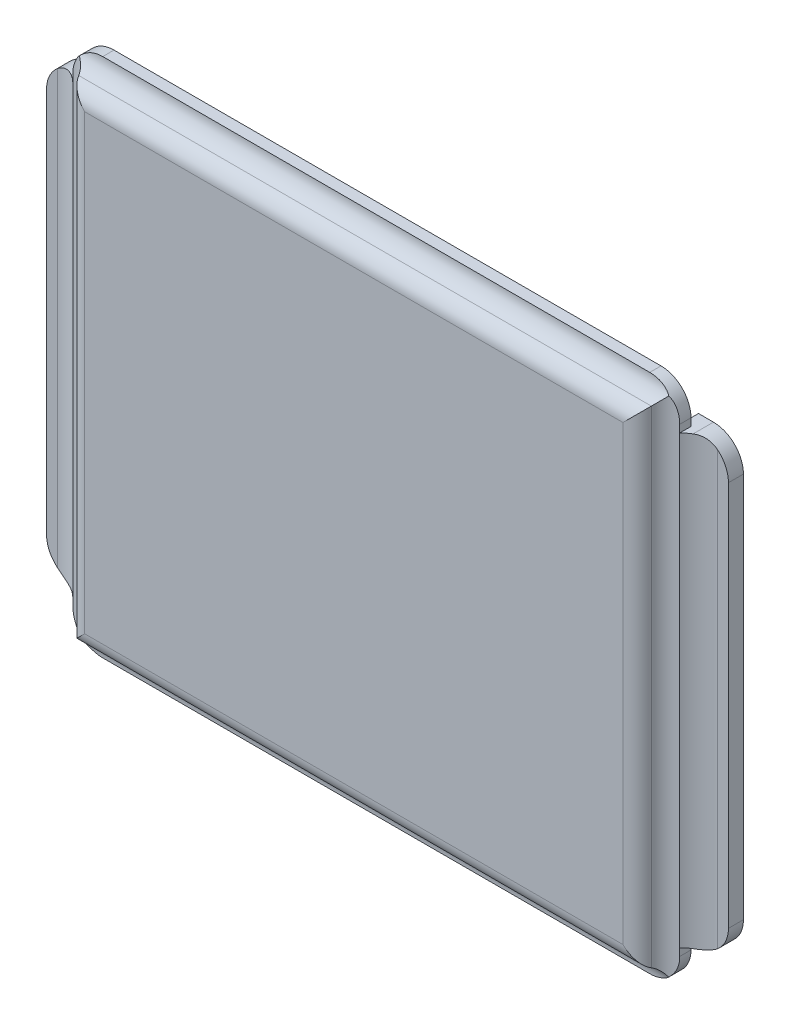
SolidWorks part; units mm, degrees
ref_plane "Front Plane" through (0, 0, 0) normal (0, 0, 1) x (1, 0, 0)
ref_plane "Top Plane" through (0, 0, 0) normal (0, 1, 0) x (1, 0, 0)
ref_plane "Right Plane" through (0, 0, 0) normal (1, 0, 0) x (0, 0, -1)
sketch "Sketch1" plane through (0, 0, 0) normal (0, 0, 1) x (1, 0, 0)
  line L0 (0, 5.95) -> (9.1, 5.95) construction
  line L1 (0, 0) -> (0.6, 0)
  line L2 (0, 0) -> (0, 5.95)
  line L3 (0, 5.95) -> (0.6, 5.95)
  line L4 (0.6, 0) -> (0.6, 5.95)
  line L6 (9.1, 5.95) -> (8.5, 5.95)
  line L7 (9.1, 5.95) -> (9.1, 0)
  line L8 (9.1, 0) -> (8.5, 0)
  line L9 (8.5, 5.95) -> (8.5, 0)
extrude "Boss-Extrude1" add sketch "Sketch1" along normal blind 0.2
sketch "Sketch2" plane through (0, 0, 0.2) normal (0, 0, 1) x (1, 0, 0)
  line L0 (8.6, 6.45) -> (8.6, -0.5)
  line L1 (0.5, -0.5) -> (1.2, -0.5)
  line L2 (0.5, -0.5) -> (0.5, 6.45)
  line L3 (0.5, 6.45) -> (1.2, 6.45)
  line L4 (1.2, 6.45) -> (7.9, 6.45)
  line L5 (7.9, -0.5) -> (1.2, -0.5)
  line L6 (8.6, -0.5) -> (7.9, -0.5)
  line L8 (8.6, 6.45) -> (7.9, 6.45)
extrude "Boss-Extrude2" add sketch "Sketch2" along normal blind 0.15
fillet "Fillet1" radius 0.5 1 edges at (0.5, 2.975, 0.2)
fillet "Fillet2" radius 0.5 1 edges at (8.6, 2.975, 0.2)
sketch "Sketch3" plane through (0, 0, 0.35) normal (0, 0, 1) x (1, 0, 0)
  line L0 (0.5, -0.5) -> (0.75, -0.5)
  line L1 (0.5, -0.5) -> (8.6, -0.5) construction
  line L2 (0.75, -0.5) -> (0.75, -0.25)
  line L3 (8.6, 6.45) -> (8.35, 6.45)
  line L4 (8.6, 6.45) -> (0.5, 6.45) construction
  line L5 (8.35, 6.45) -> (8.35, 6.2)
  line L7 (8.35, 6.2) -> (0.75, 6.2)
  line L8 (8.35, 6.2) -> (8.35, -0.25)
  line L9 (8.35, -0.25) -> (0.75, -0.25)
  line L10 (0.75, 6.2) -> (0.75, -0.25)
extrude "Boss-Extrude3" add sketch "Sketch3" along normal blind 0.3 contours L9 L8 L7 | L7 L10 L9 region at (4.55, 2.975, 0.35)
fillet "Fillet3" radius 0.25 1 edges at (0.75, 2.975, 0.35)
fillet "Fillet4" radius 0.25 1 edges at (8.35, 2.975, 0.35)
fillet "Fillet5" radius 0.25 2 edges at (4.55, 6.2, 0.35) (4.55, -0.25, 0.35)
fillet "Fillet6" radius 0.25 4 edges at (8.35, 2.975, 0.65) (4.55, 6.2, 0.65) (4.55, -0.25, 0.65) (0.75, 2.975, 0.65)
fillet "Fillet7" radius 0.4 8 edges at (9.1, 5.95, 0.1) (8.6, 6.45, 0.275) (8.6, -0.5, 0.275) (9.1, 0, 0.1) (0, 5.95, 0.1) (0.5, 6.45, 0.275) (0, 0, 0.1) (0.5, -0.5, 0.275)
